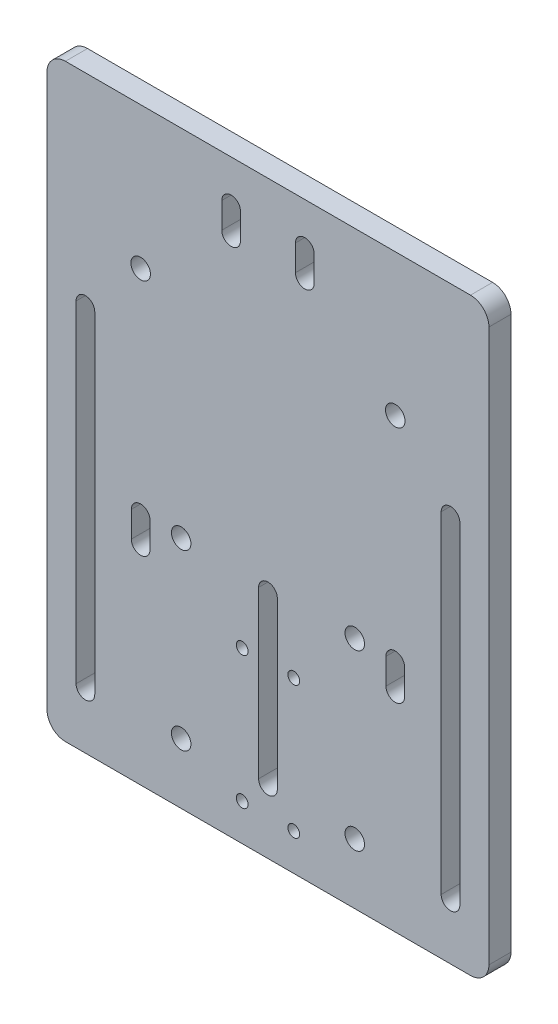
SolidWorks part; units mm, degrees
ref_plane "Front Plane" through (0, 0, 0) normal (0, 0, 1) x (1, 0, 0)
ref_plane "Top Plane" through (0, 0, 0) normal (0, 1, 0) x (1, 0, 0)
ref_plane "Right Plane" through (0, 0, 0) normal (1, 0, 0) x (0, 0, -1)
sketch "Sketch2" plane through (0, 0, 0) normal (0, 0, 1) x (1, 0, 0)
  line L1 (-55, -80) -> (55, -80)
  line L2 (-60, -75) -> (-60, 75)
  line L3 (-55, 80) -> (55, 80)
  line L4 (60, -75) -> (60, 75)
  line L5 (-60, -80) -> (60, 80) construction
  line L6 (-60, 80) -> (60, -80) construction
  arc A0 (55, -80) -> (60, -75) centre (55, -75) ccw
  arc A1 (-55, -80) -> (-60, -75) centre (-55, -75) cw
  arc A2 (55, 80) -> (60, 75) centre (55, 75) cw
  arc A3 (-60, 75) -> (-55, 80) centre (-55, 75) cw
  point P0 (0, 0)
  dimension "D3" = 5
  dimension "D1" = 120
  dimension "D2" = 160
extrude "Boss-Extrude1" add sketch "Sketch2" along normal blind 6
sketch "Sketch3" plane through (0, 0, 6) normal (0, 0, 1) x (1, 0, 0)
  line L0 (0, -17.5) -> (0, -62.5) construction
  line L1 (2.54, -17.5) -> (2.54, -62.5)
  line L2 (-2.54, -17.5) -> (-2.54, -62.5)
  line L3 (-55, -80) -> (55, -80) construction
  arc A0 (2.54, -17.5) -> (-2.54, -17.5) centre (0, -17.5) ccw
  arc A1 (-2.54, -62.5) -> (2.54, -62.5) centre (0, -62.5) ccw
  point P3 (0, -40)
  dimension "D1" = 2.54
  dimension "D2" = 45
  dimension "D3" = 40
extrude "Cut-Extrude1" cut sketch "Sketch3" against normal blind 6
hole_wizard "M5 Clearance Hole1" positions "Sketch4" profile "Sketch5" hole size "M5" standard "ANSI Metric" end condition through all
sketch "Sketch4" plane through (0, 0, 6) normal (0, 0, 1) x (1, 0, 0)
  point P0 (-23.57, -63.57)
  point P2 (-23.57, -16.43)
  point P4 (23.57, -16.43)
  point P6 (23.57, -63.57)
  dimension "D1" = 23.57
  dimension "D2" = 23.57
  dimension "D3" = 23.57
  dimension "D4" = 47.14
sketch "Sketch5" plane through (-23.57, -63.57, 6) normal (1, 0, 0) x (0, -1, 0)
  line L0 (0, 0) -> (0, 6)
  line L1 (0, 6) -> (2.65, 6)
  line L2 (2.65, 6) -> (2.65, 0)
  line L5 (2.65, 0) -> (0, 0)
  line L11 (0, -6.35) -> (0, 107.95) construction
  dimension "Thru Hole Dia." = 5.3
  dimension "Thru Hole Depth" = 6
sketch "Sketch6" plane through (0, 0, 6) normal (0, 0, 1) x (1, 0, 0)
  line L0 (-34.57, -16.43) -> (-34.57, -23.43) construction
  line L1 (-32.03, -16.43) -> (-32.03, -23.43)
  line L2 (-37.11, -16.43) -> (-37.11, -23.43)
  arc A0 (-32.03, -16.43) -> (-37.11, -16.43) centre (-34.57, -16.43) ccw
  arc A1 (-37.11, -23.43) -> (-32.03, -23.43) centre (-34.57, -23.43) ccw
  point P2 (-34.57, -19.93)
  dimension "D1" = 2.54
  dimension "D2" = 7
  dimension "D3" = 11
extrude "Cut-Extrude2" cut sketch "Sketch6" against normal blind 22
hole_wizard "M5 Clearance Hole2" positions "Sketch7" profile "Sketch8" hole size "M5" standard "ANSI Metric" end condition through all
sketch "Sketch7" plane through (0, 0, 6) normal (0, 0, 1) x (1, 0, 0)
  point P0 (-34.57, 41.47)
  dimension "D1" = 61.4
sketch "Sketch8" plane through (-34.57, 41.47, 6) normal (1, 0, 0) x (0, -1, 0)
  line L0 (0, 0) -> (0, 6)
  line L1 (0, 6) -> (2.65, 6)
  line L2 (2.65, 6) -> (2.65, 0)
  line L5 (2.65, 0) -> (0, 0)
  line L11 (0, -6.35) -> (0, 107.95) construction
  dimension "Thru Hole Dia." = 5.3
  dimension "Thru Hole Depth" = 6
sketch "Sketch9" plane through (0, 0, 6) normal (0, 0, 1) x (1, 0, 0)
  line L0 (-49.57, 25.07) -> (-49.57, -64.93) construction
  line L1 (-47.03, 25.07) -> (-47.03, -64.93)
  line L2 (-52.11, 25.07) -> (-52.11, -64.93)
  arc A0 (-47.03, 25.07) -> (-52.11, 25.07) centre (-49.57, 25.07) ccw
  arc A1 (-52.11, -64.93) -> (-47.03, -64.93) centre (-49.57, -64.93) ccw
  point P2 (-49.57, -19.93)
  dimension "D2" = 2.54
  dimension "D1" = 15
  dimension "D3" = 90
extrude "Cut-Extrude3" cut sketch "Sketch9" against normal blind 6
sketch "Sketch10" plane through (0, 0, 6) normal (0, 0, 1) x (1, 0, 0)
  line L0 (0, 85.855) -> (0, -97.3195) construction
mirror "Mirror2" about plane through (0, 0, 0) normal (1, 0, 0) of "M5 Clearance Hole2", "Cut-Extrude3", "Cut-Extrude2"
sketch "Sketch11" plane through (0, 0, 6) normal (0, 0, 1) x (1, 0, 0)
  line L0 (-10, 68.5) -> (-10, 61.5) construction
  line L1 (-7.46, 68.5) -> (-7.46, 61.5)
  line L2 (-12.54, 68.5) -> (-12.54, 61.5)
  line L3 (10, 68.5) -> (10, 61.5) construction
  line L4 (12.54, 68.5) -> (12.54, 61.5)
  line L5 (7.46, 68.5) -> (7.46, 61.5)
  line L9 (55, 80) -> (-55, 80) construction
  arc A0 (-7.46, 68.5) -> (-12.54, 68.5) centre (-10, 68.5) ccw
  arc A1 (-12.54, 61.5) -> (-7.46, 61.5) centre (-10, 61.5) ccw
  arc A2 (12.54, 68.5) -> (7.46, 68.5) centre (10, 68.5) ccw
  arc A3 (7.46, 61.5) -> (12.54, 61.5) centre (10, 61.5) ccw
  point P2 (-10, 65)
  point P7 (10, 65)
  dimension "D1" = 2.54
  dimension "D4" = 10
  dimension "D2" = 7
  dimension "D3" = 20
  dimension "D5" = 15
extrude "Cut-Extrude4" cut sketch "Sketch11" against normal blind 6
hole_wizard "M3 Clearance Hole1" positions "Sketch12" profile "Sketch13" hole size "M3" standard "ANSI Metric"
sketch "Sketch12" plane through (0, 0, 6) normal (0, 0, 1) x (1, 0, 0)
  line L0 (0, 85.855) -> (0, -97.3195) construction
  line L1 (-55, -80) -> (55, -80) construction
  point P0 (-7, -34)
  point P2 (7, -34)
  point P4 (7, -70)
  point P6 (-7, -70)
  dimension "D1" = 7
  dimension "D2" = 14
  dimension "D3" = 36
  dimension "D4" = 10
sketch "Sketch13" plane through (-7, -34, 6) normal (1, 0, 0) x (0, -1, 0)
  line L0 (0, 0) -> (0, 10.9614)
  line L1 (0, 10.9614) -> (1.6, 10)
  line L2 (1.6, 10) -> (1.6, 0)
  line L5 (1.6, 0) -> (0, 0)
  line L10 (0, 10.9614) -> (-1.6, 10) construction
  line L11 (0, -6.35) -> (0, 107.95) construction
  dimension "Hole Dia." = 3.2
  dimension "Hole Depth" = 10
  dimension "Drill Angle" = 118
